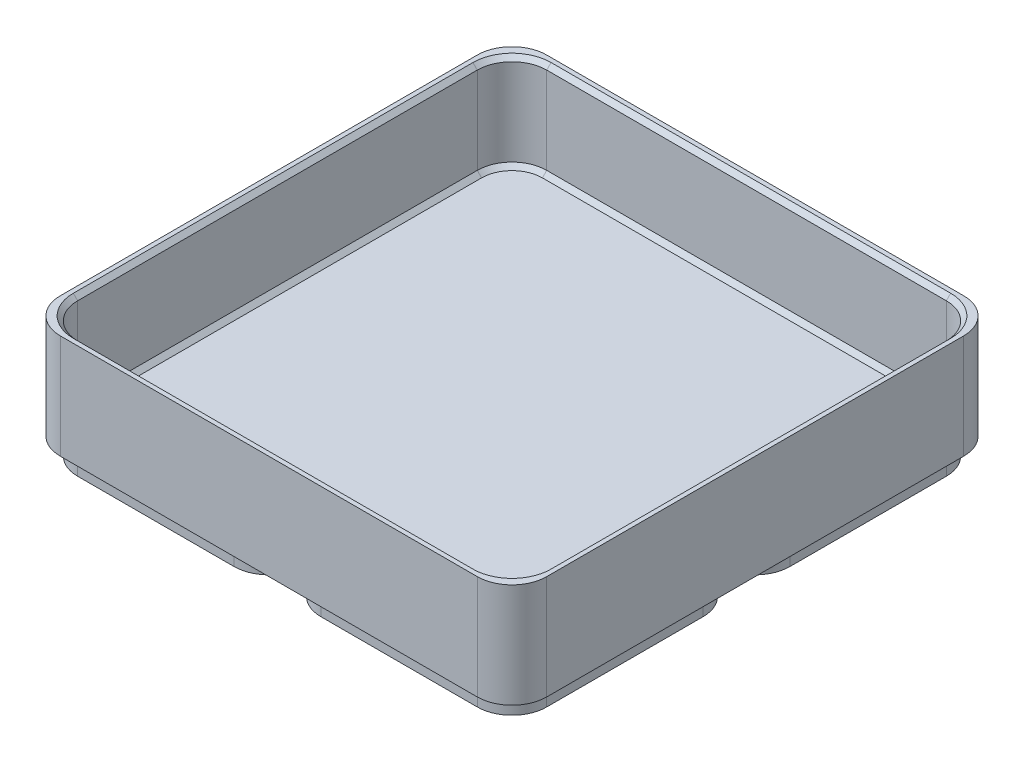
SolidWorks part; units mm, degrees
ref_plane "Front Plane" through (0, 0, 0) normal (0, 0, 1) x (1, 0, 0)
ref_plane "Top Plane" through (0, 0, 0) normal (0, 1, 0) x (1, 0, 0)
ref_plane "Right Plane" through (0, 0, 0) normal (1, 0, 0) x (0, 0, -1)
sketch "Sketch5" plane through (0, 0, 0) normal (0, 1, 0) x (1, 0, 0)
  line L1 (-22.5, -32.5) -> (22.5, -32.5)
  line L2 (-32.5, -22.5) -> (-32.5, 22.5)
  line L3 (-22.5, 32.5) -> (22.5, 32.5)
  line L4 (32.5, -22.5) -> (32.5, 22.5)
  line L5 (-32.5, -32.5) -> (32.5, 32.5) construction
  line L6 (-32.5, 32.5) -> (32.5, -32.5) construction
  arc A0 (-22.5, -32.5) -> (-32.5, -22.5) centre (-22.5, -22.5) cw
  arc A1 (22.5, -32.5) -> (32.5, -22.5) centre (22.5, -22.5) ccw
  arc A2 (22.5, 32.5) -> (32.5, 22.5) centre (22.5, 22.5) cw
  arc A3 (-32.5, 22.5) -> (-22.5, 32.5) centre (-22.5, 22.5) cw
  point P0 (0, 0)
  dimension "D3" = 10
  dimension "D1" = 65
  dimension "D2" = 65
extrude "Boss-Extrude4" add sketch "Sketch5" along normal blind 5
sketch "Sketch6" plane through (0, 5, 0) normal (0, 1, 0) x (1, 0, 0)
  line L1 (35, 35) -> (-35, 35)
  line L2 (35, 35) -> (35, -35)
  line L3 (35, -35) -> (-35, -35)
  line L4 (-35, 35) -> (-35, -35)
  line L5 (35, 35) -> (-35, -35) construction
  line L6 (35, -35) -> (-35, 35) construction
  point P0 (0, 0)
extrude "Boss-Extrude5" add sketch "Sketch6" along normal blind 30
sketch "Sketch8" plane through (0, 0, 0) normal (0, -1, 0) x (1, 0, 0)
  line L0 (-29.5711, 29.5711) -> (-22.5, 22.5)
  arc A0 (-22.5, 32.5) -> (-32.5, 22.5) centre (-22.5, 22.5) ccw construction
  circle A1 centre (-26.0355, 26.0355) radius 3
  circle A2 centre (26.0365, 26.0365) radius 3
  circle A3 centre (26.0375, -26.0355) radius 3
  circle A4 centre (-26.0345, -26.0365) radius 3
  point P8 (0, 0)
  point P15 (0.001, 0.001)
  point P18 (0.002, 0)
  point P21 (0.001, -0.001)
  point P22 (0.001, 0)
  dimension "D1" = 4
extrude "Cut-Extrude1" cut sketch "Sketch8" against normal blind 2 contours A3 | A2 | L0 A1 | L0 A1 | A4 region at (-25.1352, 0, 26.9359) region at (-26.9359, 0, 25.1352) region at (26.0365, 0, 26.0365) region at (26.0375, 0, -26.0355) region at (-26.0345, 0, -26.0365)
mirror "Mirror1" about plane through (-35, 35, -35) normal (1, 0, 0) of bodies 112
mirror "Mirror2" about plane through (35, 35, 35) normal (0, 0, -1) of bodies 113
sketch "Sketch9" plane through (0, 35, 0) normal (0, 1, 0) x (1, 0, 0)
  line L12 (32.5, 32.5) -> (-102.5, 32.5)
  line L13 (-102.5, 32.5) -> (-102.5, -102.5)
  line L14 (-102.5, -102.5) -> (32.5, -102.5)
  line L15 (32.5, -102.5) -> (32.5, 32.5)
  line L16 (22.5, 32.5) -> (-92.5, 32.5)
  line L17 (-102.5, 22.5) -> (-102.5, -92.5)
  line L18 (-92.5, -102.5) -> (22.5, -102.5)
  line L19 (32.5, -92.5) -> (32.5, 22.5)
  arc A0 (-102.5, -92.5) -> (-92.5, -102.5) centre (-92.5, -92.5) ccw
  arc A1 (22.5, -102.5) -> (32.5, -92.5) centre (22.5, -92.5) ccw
  arc A2 (22.5, 32.5) -> (32.5, 22.5) centre (22.5, 22.5) cw
  arc A3 (-92.5, 32.5) -> (-102.5, 22.5) centre (-92.5, 22.5) ccw
  dimension "D2" = 10
  dimension "D1" = 2.5
extrude "Cut-Extrude3" cut sketch "Sketch9" against normal blind 30
sketch "Sketch10" plane through (0, 5, 0) normal (0, -1, 0) x (1, 0, 0)
  line L8 (35, -35) -> (35, 105)
  line L9 (35, 105) -> (-105, 105)
  line L10 (-105, 105) -> (-105, -35)
  line L11 (-105, -35) -> (35, -35)
  line L12 (35, -35) -> (35, 105)
  line L13 (35, 105) -> (-105, 105)
  line L14 (-105, 105) -> (-105, -35)
  line L15 (-105, -35) -> (35, -35)
  dimension "D1" = 0
extrude "Boss-Extrude6" add sketch "Sketch10" against normal blind 2.5
combine bodies "Combine1" operation type add bodies to combine 117 118 119 116 120
fillet "Fillet1" radius 10 4 edges at (-105, 20, -35) (-105, 20, 105) (35, 20, 105) (35, 20, -35)
chamfer "Chamfer1" distance 1.25 angle 45 16 edges at (-35, 7.5, 102.5) (29.5711, 7.5, 99.5711) (-99.5711, 7.5, 99.5711) (32.5, 7.5, 35) (-102.5, 7.5, 35) (29.5711, 7.5, -29.5711) (-99.5711, 7.5, -29.5711) (-35, 7.5, -32.5) (29.5711, 35, 99.5711) (32.5, 35, 35) (-35, 35, 102.5) (29.5711, 35, -29.5711) (-99.5711, 35, 99.5711) (-35, 35, -32.5) (-102.5, 35, 35) (-99.5711, 35, -29.5711)
